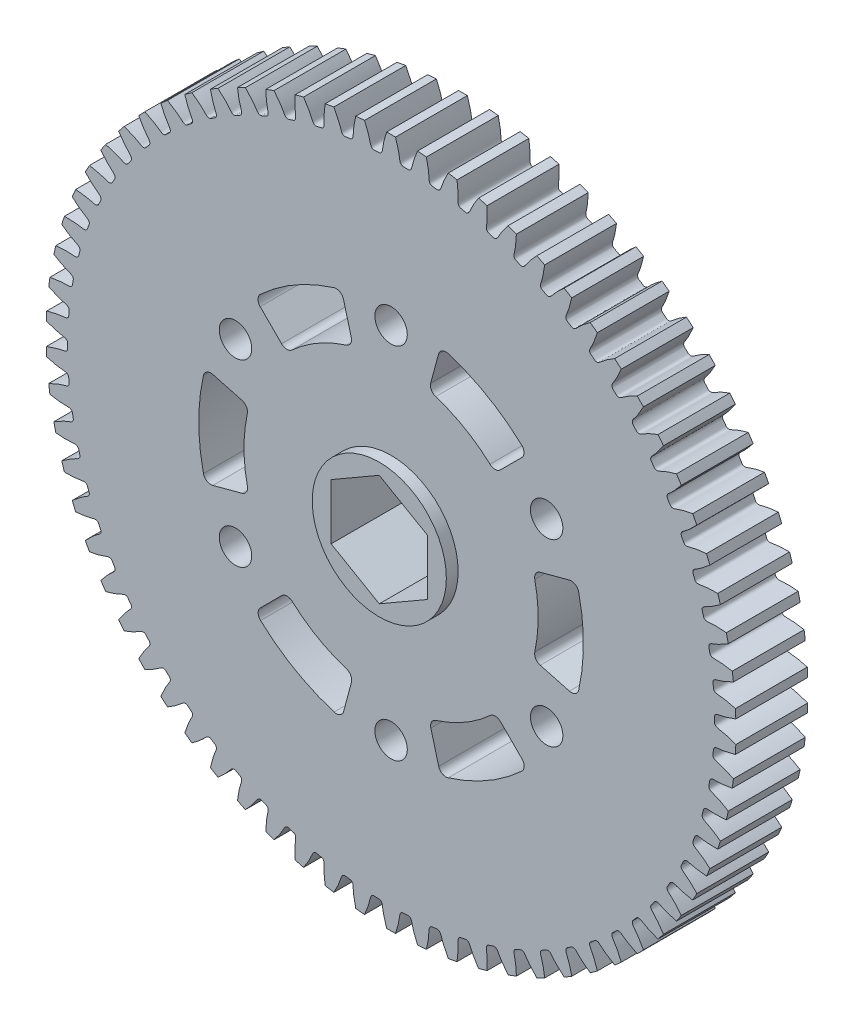
SolidWorks part; units mm, degrees
ref_plane "Front Plane" through (0, 0, 0) normal (0, 0, 1) x (1, 0, 0)
ref_plane "Top Plane" through (0, 0, 0) normal (0, 1, 0) x (1, 0, 0)
ref_plane "Right Plane" through (0, 0, 0) normal (1, 0, 0) x (0, 0, -1)
ref_plane "Plane1" through (0, 0, -4.7625) normal (0, 0, -1) x (-1, 0, 0)
sketch "Sketch1" plane through (0, 0, -4.7625) normal (0, 0, -1) x (-1, 0, 0)
  arc A0 (-45.3812, -5.5556) -> (-45.2238, -6.7177) centre (0, 0) ccw
  arc A1 (-44.7005, -9.6011) -> (-44.4396, -10.7445) centre (0, 0) ccw
  arc A2 (-43.6599, -13.5694) -> (-43.2975, -14.6848) centre (0, 0) ccw
  arc A3 (-42.2678, -17.4284) -> (-41.8069, -18.5068) centre (0, 0) ccw
  arc A4 (-40.5354, -21.1471) -> (-39.9797, -22.1799) centre (0, 0) ccw
  arc A5 (-38.4766, -24.6956) -> (-37.8305, -25.6743) centre (0, 0) ccw
  arc A6 (-36.108, -28.0452) -> (-35.3768, -28.9621) centre (0, 0) ccw
  arc A7 (-33.4487, -31.169) -> (-32.6382, -32.0166) centre (0, 0) ccw
  arc A8 (-30.5201, -34.0418) -> (-29.6369, -34.8134) centre (0, 0) ccw
  arc A9 (-27.3457, -36.6406) -> (-26.3969, -37.3299) centre (0, 0) ccw
  arc A10 (-23.9512, -38.9443) -> (-22.9445, -39.5458) centre (0, 0) ccw
  arc A11 (-20.3638, -40.9345) -> (-19.3072, -41.4433) centre (0, 0) ccw
  arc A12 (-16.6125, -42.5951) -> (-15.5145, -43.0072) centre (0, 0) ccw
  arc A13 (-12.7274, -43.9128) -> (-11.597, -44.2248) centre (0, 0) ccw
  arc A14 (-8.7399, -44.8769) -> (-7.586, -45.0863) centre (0, 0) ccw
  arc A15 (-4.682, -45.4796) -> (-3.514, -45.5848) centre (0, 0) ccw
  arc A16 (-0.5864, -45.7162) -> (0.5864, -45.7162) centre (0, 0) ccw
  arc A17 (3.514, -45.5848) -> (4.682, -45.4796) centre (0, 0) ccw
  arc A18 (7.586, -45.0863) -> (8.7399, -44.8769) centre (0, 0) ccw
  arc A19 (11.597, -44.2248) -> (12.7274, -43.9128) centre (0, 0) ccw
  arc A20 (15.5146, -43.0072) -> (16.6125, -42.5951) centre (0, 0) ccw
  arc A21 (19.3072, -41.4433) -> (20.3638, -40.9345) centre (0, 0) ccw
  arc A22 (22.9445, -39.5458) -> (23.9512, -38.9443) centre (0, 0) ccw
  arc A23 (26.3969, -37.3299) -> (27.3457, -36.6406) centre (0, 0) ccw
  arc A24 (29.6369, -34.8134) -> (30.5201, -34.0418) centre (0, 0) ccw
  arc A25 (32.6382, -32.0166) -> (33.4487, -31.169) centre (0, 0) ccw
  arc A26 (35.3768, -28.9621) -> (36.108, -28.0452) centre (0, 0) ccw
  arc A27 (37.8305, -25.6743) -> (38.4766, -24.6956) centre (0, 0) ccw
  arc A28 (39.9797, -22.1799) -> (40.5354, -21.1471) centre (0, 0) ccw
  arc A29 (41.8069, -18.5068) -> (42.2678, -17.4284) centre (0, 0) ccw
  arc A30 (43.2975, -14.6848) -> (43.6599, -13.5694) centre (0, 0) ccw
  arc A31 (44.4396, -10.7445) -> (44.7005, -9.6011) centre (0, 0) ccw
  arc A32 (45.2238, -6.7177) -> (45.3812, -5.5556) centre (0, 0) ccw
  arc A33 (45.6439, -2.6368) -> (45.6965, -1.4653) centre (0, 0) ccw
  arc A34 (45.6965, 1.4653) -> (45.6439, 2.6368) centre (0, 0) ccw
  arc A35 (45.3812, 5.5556) -> (45.2238, 6.7177) centre (0, 0) ccw
  arc A36 (44.7005, 9.6011) -> (44.4396, 10.7445) centre (0, 0) ccw
  arc A37 (43.6599, 13.5694) -> (43.2975, 14.6848) centre (0, 0) ccw
  arc A38 (42.2678, 17.4284) -> (41.8069, 18.5068) centre (0, 0) ccw
  arc A39 (40.5354, 21.1471) -> (39.9797, 22.1799) centre (0, 0) ccw
  arc A40 (38.4766, 24.6956) -> (37.8305, 25.6743) centre (0, 0) ccw
  arc A41 (36.108, 28.0452) -> (35.3768, 28.9621) centre (0, 0) ccw
  arc A42 (33.4487, 31.169) -> (32.6382, 32.0166) centre (0, 0) ccw
  arc A43 (30.5201, 34.0418) -> (29.6369, 34.8134) centre (0, 0) ccw
  arc A44 (27.3457, 36.6406) -> (26.3969, 37.3299) centre (0, 0) ccw
  arc A45 (23.9512, 38.9443) -> (22.9445, 39.5458) centre (0, 0) ccw
  arc A46 (20.3638, 40.9345) -> (19.3072, 41.4433) centre (0, 0) ccw
  arc A47 (16.6125, 42.5951) -> (15.5146, 43.0072) centre (0, 0) ccw
  arc A48 (12.7274, 43.9128) -> (11.597, 44.2248) centre (0, 0) ccw
  arc A49 (8.7399, 44.8769) -> (7.586, 45.0863) centre (0, 0) ccw
  arc A50 (4.682, 45.4796) -> (3.514, 45.5848) centre (0, 0) ccw
  arc A51 (0.5864, 45.7162) -> (-0.5864, 45.7162) centre (0, 0) ccw
  arc A52 (-3.514, 45.5848) -> (-4.682, 45.4796) centre (0, 0) ccw
  arc A53 (-7.586, 45.0863) -> (-8.7399, 44.8769) centre (0, 0) ccw
  arc A54 (-11.597, 44.2248) -> (-12.7274, 43.9128) centre (0, 0) ccw
  arc A55 (-15.5145, 43.0072) -> (-16.6125, 42.5951) centre (0, 0) ccw
  arc A56 (-19.3072, 41.4433) -> (-20.3638, 40.9345) centre (0, 0) ccw
  arc A57 (-22.9445, 39.5458) -> (-23.9512, 38.9443) centre (0, 0) ccw
  arc A58 (-26.3969, 37.3299) -> (-27.3457, 36.6406) centre (0, 0) ccw
  arc A59 (-29.6369, 34.8134) -> (-30.5201, 34.0418) centre (0, 0) ccw
  arc A60 (-32.6382, 32.0166) -> (-33.4487, 31.169) centre (0, 0) ccw
  arc A61 (-35.3768, 28.9621) -> (-36.108, 28.0452) centre (0, 0) ccw
  arc A62 (-37.8305, 25.6743) -> (-38.4766, 24.6956) centre (0, 0) ccw
  arc A63 (-39.9797, 22.1799) -> (-40.5354, 21.1471) centre (0, 0) ccw
  arc A64 (-41.8069, 18.5068) -> (-42.2678, 17.4284) centre (0, 0) ccw
  arc A65 (-43.2975, 14.6848) -> (-43.6599, 13.5694) centre (0, 0) ccw
  arc A66 (-44.4396, 10.7445) -> (-44.7005, 9.6011) centre (0, 0) ccw
  arc A67 (-45.2238, 6.7177) -> (-45.3812, 5.5556) centre (0, 0) ccw
  arc A68 (-45.6439, 2.6368) -> (-45.6965, 1.4653) centre (0, 0) ccw
  arc A69 (-45.6965, -1.4653) -> (-45.6439, -2.6368) centre (0, 0) ccw
  spline S0 degree 3 number of poles 75 (-45.2238, -6.7177) -> (-44.7005, -9.6011)
  spline S1 degree 3 number of poles 75 (-44.4396, -10.7445) -> (-43.6599, -13.5694)
  spline S2 degree 3 number of poles 75 (-43.2975, -14.6848) -> (-42.2678, -17.4284)
  spline S3 degree 3 number of poles 75 (-41.8069, -18.5068) -> (-40.5354, -21.1471)
  spline S4 degree 3 number of poles 75 (-39.9797, -22.1799) -> (-38.4766, -24.6956)
  spline S5 degree 3 number of poles 75 (-37.8305, -25.6743) -> (-36.108, -28.0452)
  spline S6 degree 3 number of poles 75 (-35.3768, -28.9621) -> (-33.4487, -31.169)
  spline S7 degree 3 number of poles 75 (-32.6382, -32.0166) -> (-30.5201, -34.0418)
  spline S8 degree 3 number of poles 75 (-29.6369, -34.8134) -> (-27.3457, -36.6406)
  spline S9 degree 3 number of poles 75 (-26.3969, -37.3299) -> (-23.9512, -38.9443)
  spline S10 degree 3 number of poles 75 (-22.9445, -39.5458) -> (-20.3638, -40.9345)
  spline S11 degree 3 number of poles 75 (-19.3072, -41.4433) -> (-16.6125, -42.5951)
  spline S12 degree 3 number of poles 75 (-15.5145, -43.0072) -> (-12.7274, -43.9128)
  spline S13 degree 3 number of poles 75 (-11.597, -44.2248) -> (-8.7399, -44.8769)
  spline S14 degree 3 number of poles 75 (-7.586, -45.0863) -> (-4.682, -45.4796)
  spline S15 degree 3 number of poles 75 (-3.514, -45.5848) -> (-0.5864, -45.7162)
  spline S16 degree 3 number of poles 75 (0.5864, -45.7162) -> (3.514, -45.5848)
  spline S17 degree 3 number of poles 75 (4.682, -45.4796) -> (7.586, -45.0863)
  spline S18 degree 3 number of poles 75 (8.7399, -44.8769) -> (11.597, -44.2248)
  spline S19 degree 3 number of poles 75 (12.7274, -43.9128) -> (15.5146, -43.0072)
  spline S20 degree 3 number of poles 75 (16.6125, -42.5951) -> (19.3072, -41.4433)
  spline S21 degree 3 number of poles 75 (20.3638, -40.9345) -> (22.9445, -39.5458)
  spline S22 degree 3 number of poles 75 (23.9512, -38.9443) -> (26.3969, -37.3299)
  spline S23 degree 3 number of poles 75 (27.3457, -36.6406) -> (29.6369, -34.8134)
  spline S24 degree 3 number of poles 75 (30.5201, -34.0418) -> (32.6382, -32.0166)
  spline S25 degree 3 number of poles 75 (33.4487, -31.169) -> (35.3768, -28.9621)
  spline S26 degree 3 number of poles 75 (36.108, -28.0452) -> (37.8305, -25.6743)
  spline S27 degree 3 number of poles 75 (38.4766, -24.6956) -> (39.9797, -22.1799)
  spline S28 degree 3 number of poles 75 (40.5354, -21.1471) -> (41.8069, -18.5068)
  spline S29 degree 3 number of poles 75 (42.2678, -17.4284) -> (43.2975, -14.6848)
  spline S30 degree 3 number of poles 75 (43.6599, -13.5694) -> (44.4396, -10.7445)
  spline S31 degree 3 number of poles 75 (44.7005, -9.6011) -> (45.2238, -6.7177)
  spline S32 degree 3 number of poles 75 (45.3812, -5.5556) -> (45.6439, -2.6368)
  spline S33 degree 3 number of poles 75 (45.6965, -1.4653) -> (45.6965, 1.4653)
  spline S34 degree 3 number of poles 75 (45.6439, 2.6368) -> (45.3812, 5.5556)
  spline S35 degree 3 number of poles 75 (45.2238, 6.7177) -> (44.7005, 9.6011)
  spline S36 degree 3 number of poles 75 (44.4396, 10.7445) -> (43.6599, 13.5694)
  spline S37 degree 3 number of poles 75 (43.2975, 14.6848) -> (42.2678, 17.4284)
  spline S38 degree 3 number of poles 75 (41.8069, 18.5068) -> (40.5354, 21.1471)
  spline S39 degree 3 number of poles 75 (39.9797, 22.1799) -> (38.4766, 24.6956)
  spline S40 degree 3 number of poles 75 (37.8305, 25.6743) -> (36.108, 28.0452)
  spline S41 degree 3 number of poles 75 (35.3768, 28.9621) -> (33.4487, 31.169)
  spline S42 degree 3 number of poles 75 (32.6382, 32.0166) -> (30.5201, 34.0418)
  spline S43 degree 3 number of poles 75 (29.6369, 34.8134) -> (27.3457, 36.6406)
  spline S44 degree 3 number of poles 75 (26.3969, 37.3299) -> (23.9512, 38.9443)
  spline S45 degree 3 number of poles 75 (22.9445, 39.5458) -> (20.3638, 40.9345)
  spline S46 degree 3 number of poles 75 (19.3072, 41.4433) -> (16.6125, 42.5951)
  spline S47 degree 3 number of poles 75 (15.5146, 43.0072) -> (12.7274, 43.9128)
  spline S48 degree 3 number of poles 75 (11.597, 44.2248) -> (8.7399, 44.8769)
  spline S49 degree 3 number of poles 75 (7.586, 45.0863) -> (4.682, 45.4796)
  spline S50 degree 3 number of poles 75 (3.514, 45.5848) -> (0.5864, 45.7162)
  spline S51 degree 3 number of poles 75 (-0.5864, 45.7162) -> (-3.514, 45.5848)
  spline S52 degree 3 number of poles 75 (-4.682, 45.4796) -> (-7.586, 45.0863)
  spline S53 degree 3 number of poles 75 (-8.7399, 44.8769) -> (-11.597, 44.2248)
  spline S54 degree 3 number of poles 75 (-12.7274, 43.9128) -> (-15.5145, 43.0072)
  spline S55 degree 3 number of poles 75 (-16.6125, 42.5951) -> (-19.3072, 41.4433)
  spline S56 degree 3 number of poles 75 (-20.3638, 40.9345) -> (-22.9445, 39.5458)
  spline S57 degree 3 number of poles 75 (-23.9512, 38.9443) -> (-26.3969, 37.3299)
  spline S58 degree 3 number of poles 75 (-27.3457, 36.6406) -> (-29.6369, 34.8134)
  spline S59 degree 3 number of poles 75 (-30.5201, 34.0418) -> (-32.6382, 32.0166)
  spline S60 degree 3 number of poles 75 (-33.4487, 31.169) -> (-35.3768, 28.9621)
  spline S61 degree 3 number of poles 75 (-36.108, 28.0452) -> (-37.8305, 25.6743)
  spline S62 degree 3 number of poles 75 (-38.4766, 24.6956) -> (-39.9797, 22.1799)
  spline S63 degree 3 number of poles 75 (-40.5354, 21.1471) -> (-41.8069, 18.5068)
  spline S64 degree 3 number of poles 75 (-42.2678, 17.4284) -> (-43.2975, 14.6848)
  spline S65 degree 3 number of poles 75 (-43.6599, 13.5694) -> (-44.4396, 10.7445)
  spline S66 degree 3 number of poles 75 (-44.7005, 9.6011) -> (-45.2238, 6.7177)
  spline S67 degree 3 number of poles 75 (-45.3812, 5.5556) -> (-45.6439, 2.6368)
  spline S68 degree 3 number of poles 75 (-45.6965, 1.4653) -> (-45.6965, -1.4653)
  spline S69 degree 3 number of poles 75 (-45.6439, -2.6368) -> (-45.3812, -5.5556)
extrude "Boss-Extrude1" add sketch "Sketch1" against normal blind 9.525
sketch "Sketch2" plane through (0, 0, -4.7625) normal (0, 0, -1) x (-1, 0, 0)
  circle A0 centre (0, 0) radius 8.89
extrude "Boss-Extrude2" add sketch "Sketch2" along normal blind 1.5621
sketch "Sketch3" plane through (0, 0, 4.7625) normal (0, 0, 1) x (1, 0, 0)
  circle A0 centre (0, 0) radius 8.89
extrude "Boss-Extrude3" add sketch "Sketch3" along normal blind 1.5621
sketch "Sketch4" plane through (0, 0, 6.3246) normal (0, 0, 1) x (1, 0, 0)
  line L0 (0, 7.3763) -> (-6.3881, 3.6882)
  line L1 (-6.3881, 3.6882) -> (-6.3881, -3.6882)
  line L2 (-6.3881, -3.6882) -> (0, -7.3763)
  line L3 (0, -7.3763) -> (6.3881, -3.6882)
  line L4 (6.3881, -3.6882) -> (6.3881, 3.6882)
  line L5 (6.3881, 3.6882) -> (0, 7.3763)
extrude "Cut-Extrude1" cut sketch "Sketch4" against normal through all
sketch "Sketch5" plane through (0, 0, -4.7625) normal (0, 0, -1) x (-1, 0, 0)
  line L0 (6.5753, 24.6377) -> (5.0224, 18.8421)
  line L1 (13.8245, 13.7526) -> (18.0671, 17.9953)
  arc A0 (18.0671, 17.9953) -> (6.5753, 24.6377) centre (0, 0) ccw
  arc A1 (5.0224, 18.8421) -> (13.8245, 13.7526) centre (0, 0) cw
extrude "Cut-Extrude2" cut sketch "Sketch5" against normal through all
sketch "Sketch6" plane through (0, 0, -4.7625) normal (0, 0, -1) x (-1, 0, 0)
  line L0 (-18.0492, 18.0133) -> (-13.8065, 13.7706)
  line L1 (-4.9979, 18.8486) -> (-6.5508, 24.6442)
  arc A0 (-6.5508, 24.6442) -> (-18.0492, 18.0133) centre (0, 0) ccw
  arc A1 (-13.8065, 13.7706) -> (-4.9979, 18.8486) centre (0, 0) cw
extrude "Cut-Extrude3" cut sketch "Sketch6" against normal through all
sketch "Sketch7" plane through (0, 0, -4.7625) normal (0, 0, -1) x (-1, 0, 0)
  line L0 (-24.6245, -6.6244) -> (-18.829, -5.0715)
  line L1 (-18.8223, 5.096) -> (-24.6179, 6.6489)
  arc A0 (-24.6179, 6.6489) -> (-24.6245, -6.6244) centre (0, 0) ccw
  arc A1 (-18.829, -5.0715) -> (-18.8223, 5.096) centre (0, 0) cw
extrude "Cut-Extrude4" cut sketch "Sketch7" against normal through all
sketch "Sketch8" plane through (0, 0, -4.7625) normal (0, 0, -1) x (-1, 0, 0)
  line L0 (-6.5753, -24.6377) -> (-5.0224, -18.8421)
  line L1 (-13.8245, -13.7526) -> (-18.0671, -17.9953)
  arc A0 (-18.0671, -17.9953) -> (-6.5753, -24.6377) centre (0, 0) ccw
  arc A1 (-5.0224, -18.8421) -> (-13.8245, -13.7526) centre (0, 0) cw
extrude "Cut-Extrude5" cut sketch "Sketch8" against normal through all
sketch "Sketch9" plane through (0, 0, -4.7625) normal (0, 0, -1) x (-1, 0, 0)
  line L0 (18.0492, -18.0133) -> (13.8065, -13.7706)
  line L1 (4.9979, -18.8486) -> (6.5508, -24.6442)
  arc A0 (6.5508, -24.6442) -> (18.0492, -18.0133) centre (0, 0) ccw
  arc A1 (13.8065, -13.7706) -> (4.9979, -18.8486) centre (0, 0) cw
extrude "Cut-Extrude6" cut sketch "Sketch9" against normal through all
sketch "Sketch10" plane through (0, 0, 4.7625) normal (0, 0, 1) x (1, 0, 0)
  line L0 (-18.829, 5.0715) -> (-24.6245, 6.6244)
  line L1 (-24.6179, -6.6489) -> (-18.8223, -5.096)
  arc A0 (-24.6245, 6.6244) -> (-24.6179, -6.6489) centre (0, 0) ccw
  arc A1 (-18.8223, -5.096) -> (-18.829, 5.0715) centre (0, 0) cw
extrude "Cut-Extrude7" cut sketch "Sketch10" against normal through all
hole_wizard "Ø4.3 (4.3) Diameter Hole1" positions "Sketch12" profile "Sketch11" hole size "Ø4.3" standard "ANSI Metric"
sketch "Sketch12" plane through (0, 0, -4.7625) normal (0, 0, -1) x (-1, 0, 0)
  point P0 (0, -23.8125)
  point P1 (20.6222, -11.9062)
  point P2 (20.6222, 11.9063)
  point P3 (-20.6222, -11.9063)
  point P4 (-20.6222, 11.9062)
  point P5 (0, 23.8125)
sketch "Sketch11" plane through (0, -23.8125, -4.7625) normal (1, 0, 0) x (0, 1, 0)
  line L0 (0, 0) -> (0, 11.0871)
  line L1 (0, 11.0871) -> (2.15, 11.0871)
  line L2 (2.15, 11.0871) -> (2.15, 0)
  line L5 (2.15, 0) -> (0, 0)
  line L11 (0, -6.35) -> (0, 107.95) construction
  dimension "Thru Hole Dia." = 4.3
  dimension "Thru Hole Depth" = 11.0871
fillet "Fillet1" radius 1 24 edges at (18.8223, 5.096, 0) (-13.8245, 13.7526, 0) (4.9979, 18.8486, 0) (-24.6245, 6.6244, 0) (24.6245, -6.6244, 0) (-18.829, 5.0715, 0) (18.0492, 18.0133, 0) (-18.8223, -5.096, 0) (-6.5753, 24.6377, 0) (-6.5508, -24.6442, 0) (24.6179, 6.6489, 0) (-18.0492, -18.0133, 0) (18.829, -5.0715, 0) (-13.8065, -13.7706, 0) (6.5508, 24.6442, 0) (-4.9979, -18.8486, 0) (13.8065, 13.7706, 0) (18.0671, -17.9953, 0) (-18.0671, 17.9953, 0) (6.5753, -24.6377, 0) (-5.0224, 18.8421, 0) (5.0224, -18.8421, 0) (-24.6179, -6.6489, 0) (13.8245, -13.7526, 0) tangent propagation no
